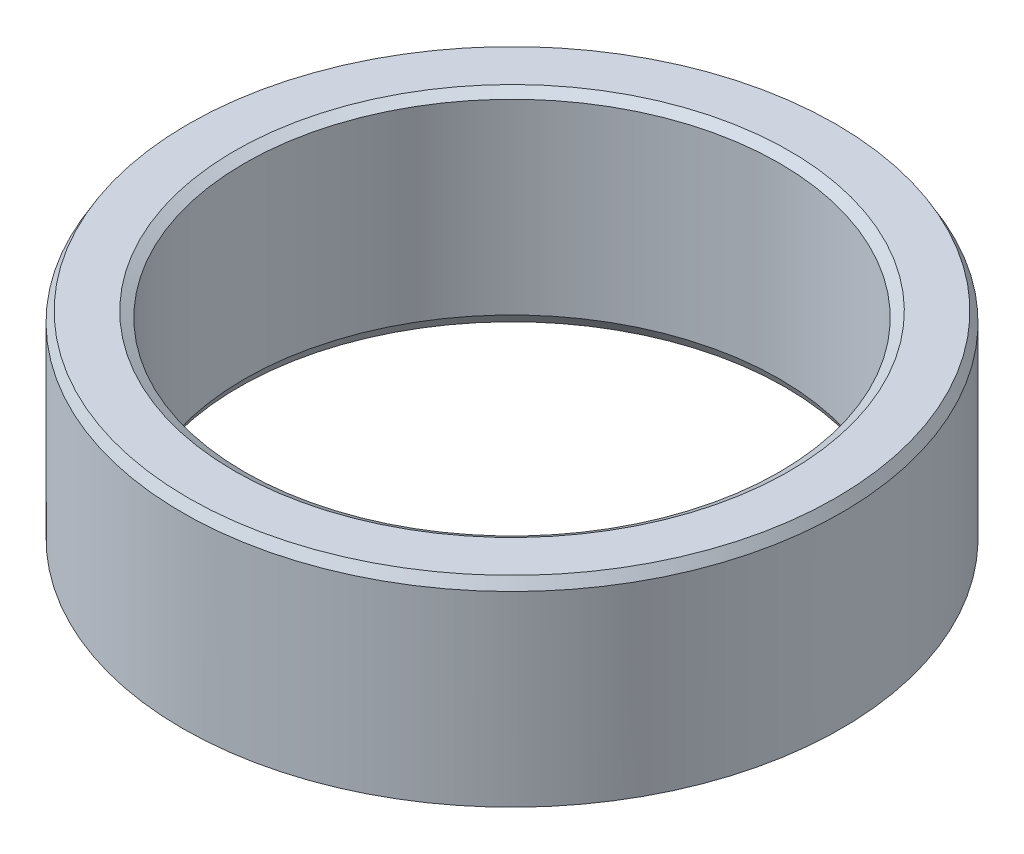
SolidWorks part; units mm, degrees
ref_plane "Front Plane" through (0, 0, 0) normal (0, 0, 1) x (1, 0, 0)
ref_plane "Top Plane" through (0, 0, 0) normal (0, 1, 0) x (1, 0, 0)
ref_plane "Right Plane" through (0, 0, 0) normal (1, 0, 0) x (0, 0, -1)
sketch "Sketch1" plane through (0, 0, 0) normal (0, 1, 0) x (1, 0, 0)
  circle A0 centre (0, 0) radius 42.5
  dimension "SLEEVE_OD" = 85
extrude "Boss-Extrude1" add sketch "Sketch1" along normal blind 26.118
sketch "Sketch2" plane through (0, 0, 0) normal (0, 1, 0) x (1, 0, 0)
  circle A0 centre (0, 0) radius 34.4935
  dimension "BORE_D" = 68.9871
extrude "Cut-Extrude1" cut sketch "Sketch2" along normal through all
chamfer "Chamfer1" distance 1.2832 angle 30 4 edges at (0, 26.118, 34.4935) (0, 0, 34.4935) (0, 0, 42.5) (0, 26.118, 42.5) first distance on face at (0, 26.118, 34.4935) first distance on face at (0, 0, 34.4935) first distance on face at (0, 26.118, 42.5)
